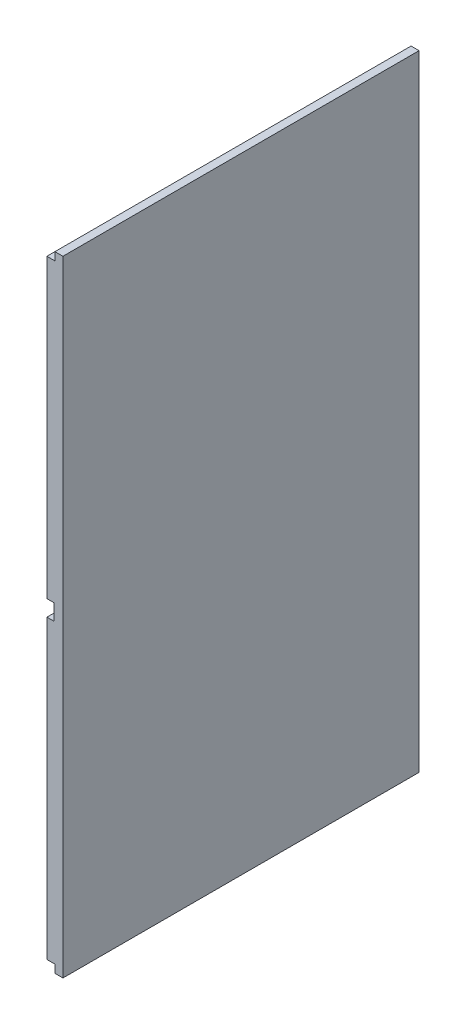
SolidWorks part; units mm, degrees
ref_plane "Front" through (0, 0, 0) normal (0, 0, 1) x (1, 0, 0)
ref_plane "Top" through (0, 0, 0) normal (0, 1, 0) x (1, 0, 0)
ref_plane "Right" through (0, 0, 0) normal (1, 0, 0) x (0, 0, -1)
sketch "Sketch1" plane through (0, 0, 0) normal (1, 0, 0) x (0, 0, -1)
  line L1 (-200, -351) -> (200, -351)
  line L2 (-200, -351) -> (-200, 351)
  line L3 (-200, 351) -> (200, 351)
  line L4 (200, -351) -> (200, 351)
  line L5 (-200, -351) -> (200, 351) construction
  line L6 (-200, 351) -> (200, -351) construction
  point P0 (0, 0)
  dimension "D1" = 400
  dimension "D2" = 702
extrude "Boss-Extrude1" add sketch "Sketch1" along normal blind 18
sketch "Sketch2" plane through (0, 0, 0) normal (-1, 0, 0) x (0, 0, 1)
  line L0 (200, 351) -> (200, -351) construction
  line L1 (-200, -351) -> (200, -351)
  line L2 (-200, -351) -> (-200, -342)
  line L3 (-200, -342) -> (200, -342)
  line L4 (200, -351) -> (200, -342)
  line L5 (-200, -351) -> (-200, 351) construction
  line L6 (200, 351) -> (-200, 351)
  line L7 (200, 351) -> (200, 342)
  line L8 (200, 342) -> (-200, 342)
  line L9 (-200, 351) -> (-200, 342)
  dimension "D1" = 9
  dimension "D2" = 9
extrude "Cut-Extrude1" cut sketch "Sketch2" against normal blind 9
sketch "Sketch3" plane through (0, 0, 0) normal (-1, 0, 0) x (0, 0, 1)
  line L0 (200, 342) -> (200, -342) construction
  line L1 (-200, -9) -> (200, -9)
  line L2 (-200, -9) -> (-200, 9)
  line L3 (-200, 9) -> (200, 9)
  line L4 (200, -9) -> (200, 9)
  line L5 (-200, -9) -> (200, 9) construction
  line L6 (-200, 9) -> (200, -9) construction
  point P0 (0, 0)
  dimension "D1" = 18
extrude "Cut-Extrude2" cut sketch "Sketch3" against normal blind 8
